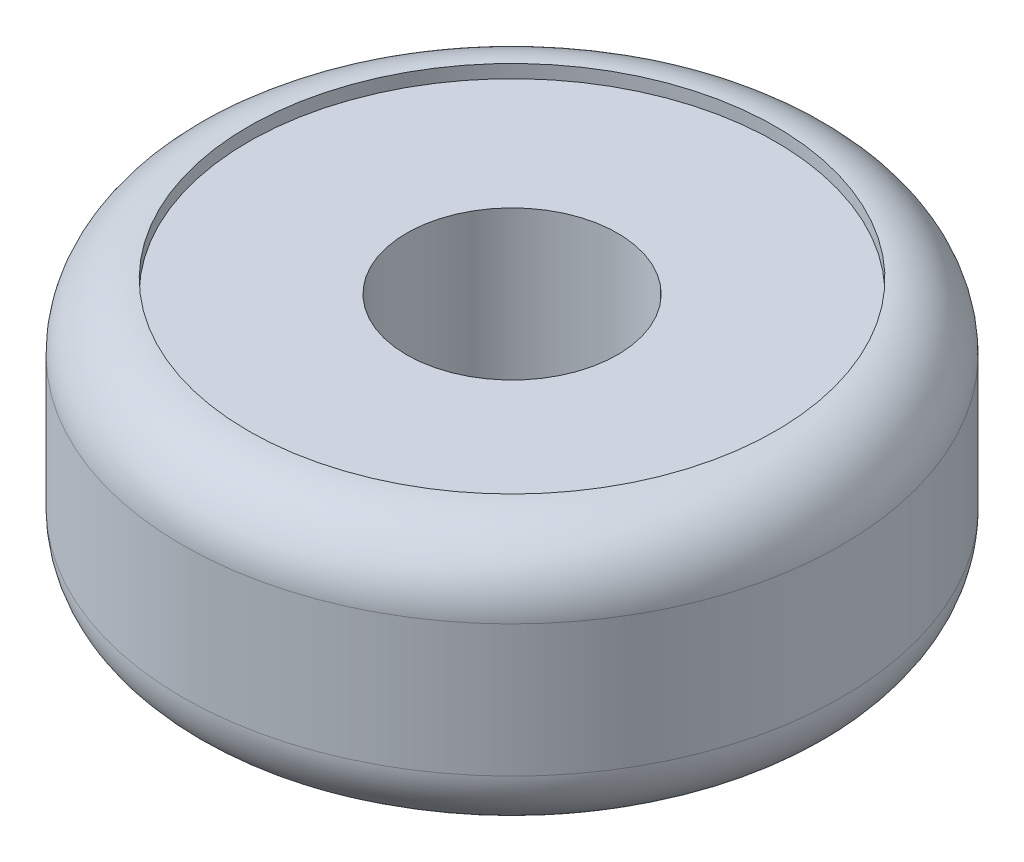
SolidWorks part; units mm, degrees
ref_plane "前视基准面" through (0, 0, 0) normal (0, 0, 1) x (1, 0, 0)
ref_plane "上视基准面" through (0, 0, 0) normal (0, 1, 0) x (1, 0, 0)
ref_plane "右视基准面" through (0, 0, 0) normal (1, 0, 0) x (0, 0, -1)
sketch "草图1" plane through (0, 0, 0) normal (0, 1, 0) x (1, 0, 0)
  circle A0 centre (0, 0) radius 1.6
  circle A1 centre (0, 0) radius 4
  dimension "D1" = 3.2
  dimension "D2" = 8
extrude "凸台-拉伸1" add sketch "草图1" along normal mid plane 3.6
sketch "草图2" plane through (0, 0, 0) normal (0, 1, 0) x (1, 0, 0)
  circle A0 centre (0, 0) radius 5
  circle A2 centre (0, 0) radius 4
  circle A3 centre (0, 0) radius 4
  dimension "D2" = 10
  dimension "D1" = 0
extrude "凸台-拉伸2" add sketch "草图2" along normal mid plane 4
fillet "圆角1" radius 1 2 edges at (0, -2, 5) (0, 2, 5)
